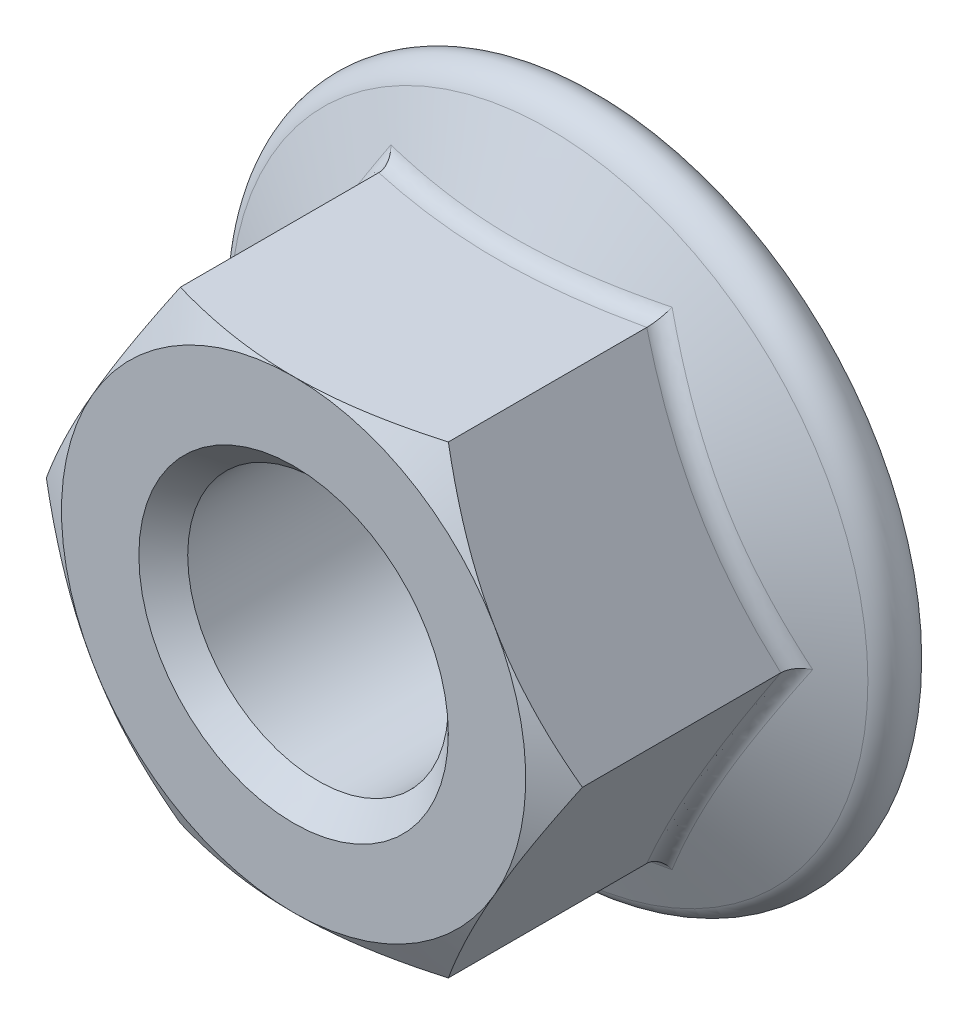
SolidWorks part; units mm, degrees
ref_plane "Front" through (0, 0, 0) normal (0, 0, 1) x (1, 0, 0)
ref_plane "Top" through (0, 0, 0) normal (0, 1, 0) x (1, 0, 0)
ref_plane "Right" through (0, 0, 0) normal (1, 0, 0) x (0, 0, -1)
other "Configuration Table"
sketch "Sketch1" plane through (0, 0, 0) normal (0, 0, 1) x (1, 0, 0)
  line L1 (5.1962, -9) -> (10.3923, 0)
  line L2 (10.3923, 0) -> (5.1962, 9)
  line L3 (5.1962, 9) -> (-5.1962, 9)
  line L4 (-5.1962, 9) -> (-10.3923, 0)
  line L5 (-10.3923, 0) -> (-5.1962, -9)
  line L6 (-5.1962, -9) -> (5.1962, -9)
  circle A0 centre (0, 0) radius 9 construction
  circle A1 centre (0, 0) radius 5.053
  dimension "D1" = 10.106
extrude "BaseNut" add sketch "Sketch1" against normal blind 12
cosmetic thread "ThreadCosmetic1" parameters "D2"=12
sketch "Sketch3" plane through (0.6779, 0, -16.6426) normal (0, 1, 0) x (0, 0, -1)
  line L0 (4.0352, 0.6779) -> (-19.0613, 0.6779) construction
  line L2 (-16.6426, 9.6779) -> (-15.8388, 11.0702)
  line L4 (-15.8388, 11.0702) -> (-16.6426, 11.0702)
  line L5 (-16.6426, 11.0702) -> (-16.6426, 9.6779)
  line L6 (-10.6426, 11.0702) -> (-10.6426, 14.238) construction
  line L8 (-4.6426, 11.0702) -> (-4.6426, 9.6779)
  line L9 (-5.4465, 11.0702) -> (-4.6426, 11.0702)
  line L10 (-4.6426, 9.6779) -> (-5.4465, 11.0702)
  line L11 (-4.6426, 11.0702) -> (-16.6426, 11.0702) construction
  dimension "D1" = 30
revolve "Double-Chamfer" cut sketch "Sketch3" angle 360 about L0
sketch "Sketch4" plane through (4.6827, 0, -16.7173) normal (0, 1, 0) x (0, 0, -1)
  line L0 (-21.7744, 4.6827) -> (9.7398, 4.6827) construction
  line L2 (-10.2238, 30.5008) -> (-10.2238, 8.9315) construction
  line L3 (-6.8143, 17.0476) -> (-10.2238, 9.7357)
  line L4 (-4.7173, 9.7357) -> (-16.7173, 9.7357) construction
  line L5 (-4.7173, 9.7357) -> (-4.7173, 16.5827)
  line L11 (-10.2238, 9.7357) -> (-4.7173, 9.7357)
  arc A0 (-4.7173, 16.5827) -> (-6.8143, 17.0476) centre (-5.8173, 16.5827) ccw
  dimension "dc" = 26
  dimension "m1" = 12
revolve "Flange" add sketch "Sketch4" angle 360 about L0
fillet "FlangeFillet" radius 0.7 6 edges at (-6.5854, -6.5937, -8.4828) (-9.003, 2.4063, -8.4828) (6.5854, 6.5937, -8.4828) (9.003, -2.4063, -8.4828)
sketch "Sketch5" plane through (-5.1971, 0, -15.1971) normal (0, 1, 0) x (0, 0, -1)
  line L0 (3.5984, -5.1971) -> (-23.9926, -5.1971) construction
  line L1 (-3.1971, -0.1441) -> (-15.1971, -0.1441) construction
  line L2 (-15.1971, 0.8029) -> (-15.1971, -0.1441)
  line L4 (-15.1971, -0.1441) -> (-14.2501, -0.1441)
  line L6 (-14.2501, -0.1441) -> (-15.1971, 0.8029)
  line L7 (-9.1971, -0.1441) -> (-9.1971, 0.9419) construction
  line L8 (-4.1441, -0.1441) -> (-3.1971, 0.8029)
  line L9 (-3.1971, -0.1441) -> (-4.1441, -0.1441)
  line L10 (-3.1971, 0.8029) -> (-3.1971, -0.1441)
  dimension "da" = 12
  dimension "D2" = 45
revolve "Hole" cut sketch "Sketch5" angle 360 about L0
sketch "Sketch6" plane through (0, 0, 0) normal (0, 1, 0) x (1, 0, 0)
  line L0 (-5.8731, 0.947) -> (-5.053, 0.4735)
  line L1 (-5.053, 0.4735) -> (-4.106, 0.4735)
  line L2 (-4.106, 0.4735) -> (-4.106, 1.4205)
  line L3 (-4.106, 1.4205) -> (-5.053, 1.4205)
  line L4 (-5.053, 1.4205) -> (-5.8731, 0.947)
  line L5 (0, 7.348) -> (0, 34.1252) construction
  dimension "D1" = 0.947
  dimension "D2" = 10.106
revolve "Cut-Revolve10" [suppressed] cut sketch "Sketch6" angle 360 about L5
pattern_linear "LPattern10" [suppressed] count 11 spacing 1.1364 along (0, 0, -1) of bodies 105
equation "\"m1@Sketch4\" = \"m@BaseNut\""
equation "\"sq@Sketch3\" = \"s@Sketch1\""
equation "\"D2@Sketch6\"=\"D1@Sketch1\""
equation "\"D1@Sketch6\"= (\"D2@ThreadCosmetic1\"  - \"D2@Sketch6\" )  / 2"
equation "\"D3@LPattern10\"=\"D1@Sketch6\" * 1.2 "
equation "\"D1@LPattern10\"=\"m@BaseNut\"  / \"D3@LPattern10\""
